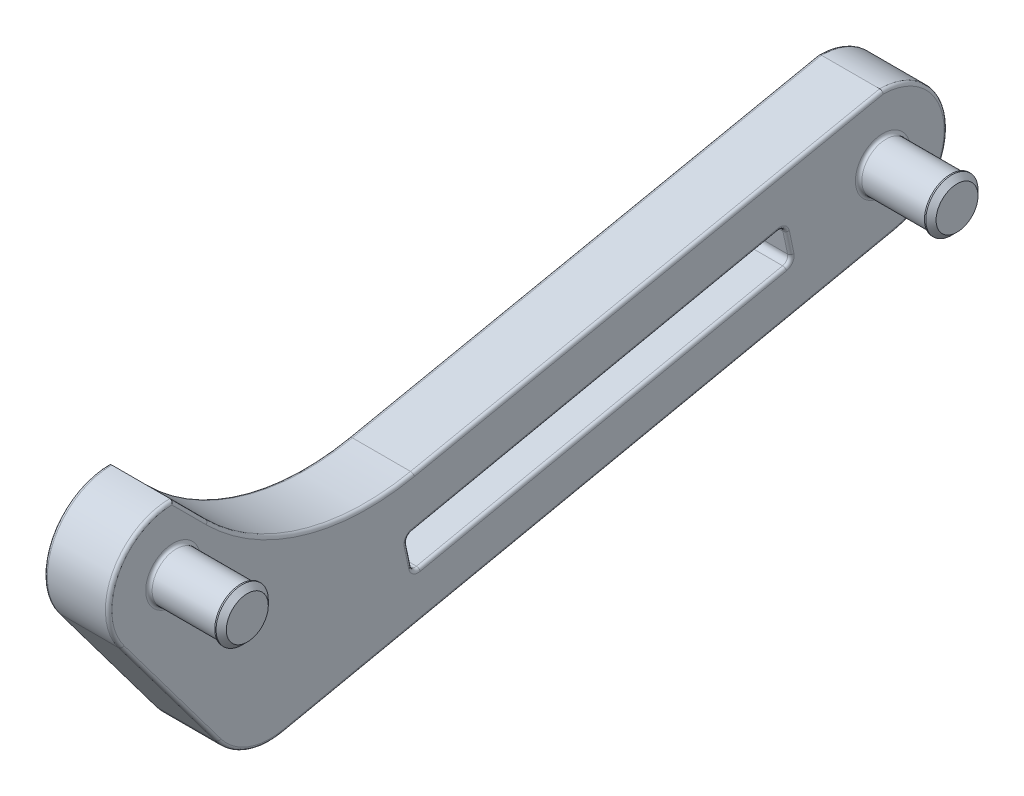
SolidWorks part; units mm, degrees
ref_plane "前视基准面" through (0, 0, 0) normal (0, 0, 1) x (1, 0, 0)
ref_plane "上视基准面" through (0, 0, 0) normal (0, 1, 0) x (1, 0, 0)
ref_plane "右视基准面" through (0, 0, 0) normal (1, 0, 0) x (0, 0, -1)
other "Configuration Table"
sketch "草图1" plane through (0, 0, 0) normal (1, 0, 0) x (0, 0, -1)
  line L0 (0, 0) -> (110, 0) construction
  line L1 (0, 10) -> (110, 10)
  line L2 (0, -10) -> (110, -10)
  arc A0 (0, 10) -> (0, -10) centre (0, 0) ccw
  arc A1 (110, -10) -> (110, 10) centre (110, 0) ccw
  circle A2 centre (0, 0) radius 3.75
  circle A3 centre (110, 0) radius 3.75
  point P3 (55, 0)
  dimension "D2" = 10
  dimension "D3" = 7.5
  dimension "D4" = 7.5
  dimension "D1" = 110
extrude "凸台-拉伸1" add sketch "草图1" along normal blind 10 contours A2 | L2 A1 L1 A0
sketch "草图2" plane through (10, 0, 0) normal (1, 0, 0) x (0, 0, -1)
  circle A0 centre (0, 0) radius 3.75 construction
  circle A1 centre (0, 0) radius 3.75
  circle A2 centre (110, 0) radius 3.75 construction
  circle A3 centre (110, 0) radius 3.75
extrude "凸台-拉伸2" add sketch "草图2" along normal mid plane 20
sketch "草图3" plane through (0, 0, 0) normal (-1, 0, 0) x (0, 0, 1)
  line L0 (0, 0) -> (-15, 0) construction
  line L1 (8, -6) -> (-7, -26)
  line L2 (0, 10) -> (-110, 10)
  line L3 (-110, -10) -> (0, -10)
  line L4 (0, 10) -> (-110, 10)
  line L6 (-17.0601, -29.7855) -> (-112.0601, -9.7855)
  line L7 (-15, 0) -> (-15, -20) construction
  arc A0 (-17.0601, -29.7855) -> (-7, -26) centre (-15, -20) ccw
  arc A2 (0, -10) -> (0, 10) centre (0, 0) ccw
  arc A3 (-110, 10) -> (-110, -10) centre (-110, 0) ccw
  arc A4 (8, -6) -> (0, 10) centre (0, 0) ccw
  arc A5 (-110, 10) -> (-112.0601, -9.7855) centre (-110, 0) ccw
  dimension "D2" = 10
  dimension "D1" = 0
extrude "凸台-拉伸3" add sketch "草图3" against normal blind 10
sketch "草图4" plane through (0, 0, 0) normal (-1, 0, 0) x (0, 0, 1)
  line L0 (0, 0) -> (-110, 0) construction
  line L1 (0, 10) -> (-5.4706, 4.5294)
  line L3 (-7, -26) -> (8, -6)
  line L4 (0, 10) -> (-110, 10)
  line L5 (-112.0601, -9.7855) -> (-17.0601, -29.7855)
  line L7 (0, 10) -> (-110, 10)
  line L9 (-37.291, -5) -> (-110, 10)
  arc A0 (-37.291, -5) -> (-5.4706, 4.5294) centre (-30.2193, 29.2782) ccw
  arc A3 (8, -6) -> (0, 10) centre (0, 0) ccw
  arc A4 (-110, 10) -> (-112.0601, -9.7855) centre (-110, 0) ccw
  arc A5 (-17.0601, -29.7855) -> (-7, -26) centre (-15, -20) ccw
  point P7 (-22.6801, -1.5903)
  point P12 (-27.0948, -4.9452)
  point P13 (-36.9093, -4.7802)
  point P14 (-36.937, -4.7962)
  point P17 (-18.5625, 0)
  point P18 (-17.5421, -2.0265)
  point P19 (-58.6398, -8.2747)
  point P20 (-36.695, -2.7069)
  point P21 (-29.0798, 0)
  point P22 (-21.5817, -10.3983)
  point P23 (-16.003, -5.6108)
  point P24 (-36.937, 0)
  dimension "D4" = 35
  dimension "D2" = 45
  dimension "D3" = 15
  dimension "D1" = 0
extrude "切除-拉伸1" cut sketch "草图4" against normal through all
sketch "草图5" plane through (0, 0, 0) normal (-1, 0, 0) x (0, 0, 1)
  line L0 (-37.2268, -18.3864) -> (-95.9398, -6.0258)
  line L1 (-95.9398, -6.0258) -> (-94.8067, -0.6438)
  line L2 (-94.8067, -0.6438) -> (-36.0937, -13.0044)
  line L3 (-36.0937, -13.0044) -> (-37.2268, -18.3864)
  line L4 (-112.0601, -9.7855) -> (-17.0601, -29.7855) construction
  line L6 (-112.0601, -9.7855) -> (-107.9824, 9.5838) construction
  line L7 (-110, 10) -> (-37.291, -5) construction
  dimension "D1" = 7
  dimension "D2" = 5.5
  dimension "D3" = 60
  dimension "D4" = 15
extrude "切除-拉伸2" cut sketch "草图5" against normal blind 10
fillet "圆角1" radius 1 4 edges at (5, -13.0044, -36.0937) (5, -18.3864, -37.2268) (5, -6.0258, -95.9398) (5, -0.6438, -94.8067)
sketch "草图6" plane through (20, 0, 0) normal (1, 0, 0) x (0, 0, -1)
  circle A1 centre (110, 0) radius 3.75
  circle A2 centre (110, 0) radius 3.75
  circle A3 centre (0, 0) radius 3.75
  circle A4 centre (0, 0) radius 3.75
  dimension "D1" = 0
  dimension "D2" = 0
extrude "凸台-拉伸4" add sketch "草图6" along normal blind 0.5
sketch "草图7" plane through (20.5, 0, 0) normal (1, 0, 0) x (0, 0, -1)
  circle A0 centre (110, 0) radius 3.75 construction
  circle A1 centre (110, 0) radius 3.75 construction
  circle A2 centre (110, 0) radius 4.05
  dimension "D1" = 8.1
extrude "凸台-拉伸5" add sketch "草图7" along normal blind 1
chamfer "倒角1" distance 0.8 angle 45 1 edges at (21.5, 0, -114.05)
sketch "草图8" plane through (20.5, 0, 0) normal (1, 0, 0) x (0, 0, -1)
  circle A0 centre (0, 0) radius 4.05
  dimension "D1" = 8.1
extrude "凸台-拉伸6" add sketch "草图8" along normal blind 1
chamfer "倒角2" distance 0.8 angle 45 1 edges at (21.5, 0, -4.05)
fillet "圆角3" radius 0.5 34 edges at (10, 0, -3.75) (10, 0, -113.75) (10, -4.2506, -20.1783) (10, 2.5, -73.6455) (10, 1.0356, -119.9462) (10, -19.7855, -64.5601) (10, -29.3593, -11.4782) (10, -16, 0.5) (10, 4.4721, 8.9443) (10, 7.2647, -2.7353) (10, -5.7995, -95.5928) (10, -3.3348, -95.3733) (10, -0.9907, -94.5805) (10, -6.8241, -65.4502) (10, -13.2307, -36.4407) (10, -15.6954, -36.6603) (10, -18.0395, -37.4531) (10, -12.2061, -66.5833) (0, -16, 0.5) (0, -29.3593, -11.4782) (0, -19.7855, -64.5601) (0, 1.0356, -119.9462) (0, 2.5, -73.6455) (0, -4.2506, -20.1783) (0, 7.2647, -2.7353) (0, 4.4721, 8.9443) (0, -0.9907, -94.5805) (0, -3.3348, -95.3733) (0, -5.7995, -95.5928) (0, -12.2061, -66.5833) (0, -18.0395, -37.4531) (0, -15.6954, -36.6603) (0, -13.2307, -36.4407) (0, -6.8241, -65.4502)
